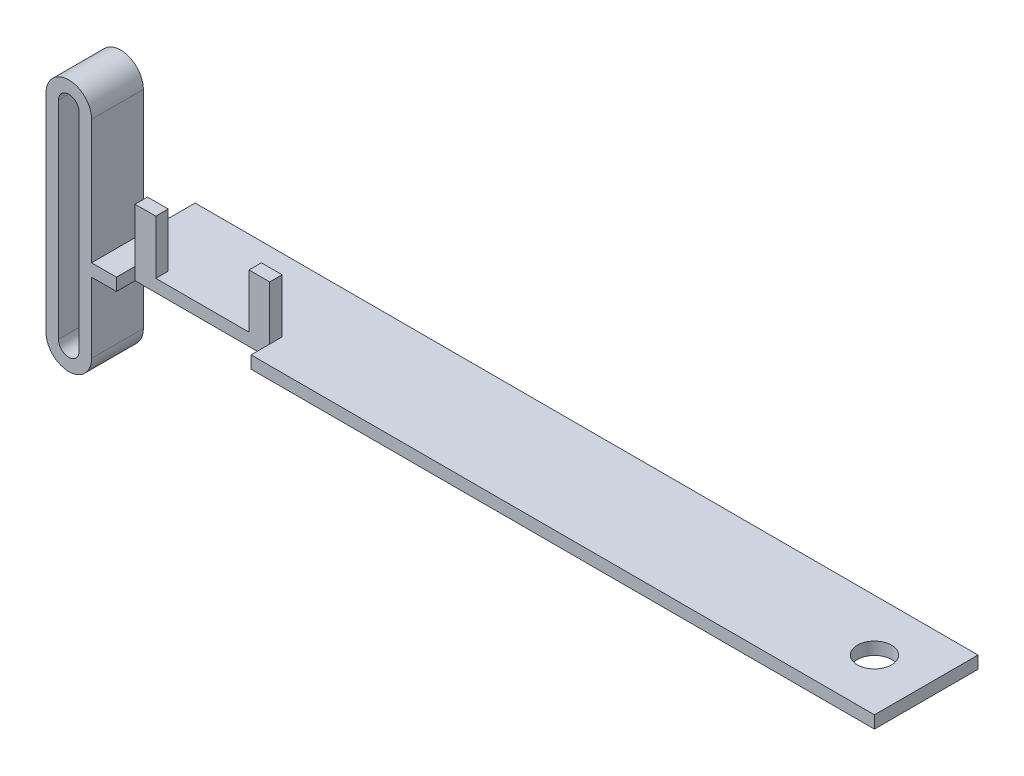
SolidWorks part; units mm, degrees
ref_plane "Front Plane" through (0, 0, 0) normal (0, 0, 1) x (1, 0, 0)
ref_plane "Top Plane" through (0, 0, 0) normal (0, 1, 0) x (1, 0, 0)
ref_plane "Right Plane" through (0, 0, 0) normal (1, 0, 0) x (0, 0, -1)
sketch "Sketch1" plane through (0, 0, 0) normal (0, 1, 0) x (1, 0, 0)
  line L1 (-100, 12.5) -> (100, 12.5)
  line L2 (-100, 12.5) -> (-100, -12.5)
  line L3 (-100, -12.5) -> (100, -12.5)
  line L4 (100, 12.5) -> (100, -12.5)
  line L5 (-100, 12.5) -> (100, -12.5) construction
  line L6 (-100, -12.5) -> (100, 12.5) construction
  circle A4 centre (87.5, 0) radius 4.125
  point P0 (0, 0)
  point P17 (100, 0)
  dimension "D3" = 12.5
  dimension "D4" = 8.25
  dimension "D1" = 25
  dimension "D2" = 200
extrude "Boss-Extrude1" add sketch "Sketch1" along normal blind 3 contours L3 L4 L1 L2 A4 | L3 region at (-0.9456, 0, 0)
sketch "Sketch2" plane through (0, 0, 0) normal (0, 0, 1) x (1, 0, 0)
  line L0 (-94.5, 33) -> (-94.5, -17) construction
  line L1 (-92, 33) -> (-92, -17)
  line L2 (-97, 33) -> (-97, -17)
  line L3 (-89, 33) -> (-89, -17)
  line L4 (-100, 33) -> (-100, -17)
  line L7 (-83, 6.4998) -> (-50.5, 6.4998)
  line L8 (-83, 6.4998) -> (-83, -3.3981)
  line L9 (-83, -3.3981) -> (-50.5, -3.3981)
  line L10 (-50.5, 6.4998) -> (-50.5, -3.3981)
  arc A0 (-92, 33) -> (-97, 33) centre (-94.5, 33) ccw
  arc A1 (-97, -17) -> (-92, -17) centre (-94.5, -17) ccw
  arc A2 (-100, -17) -> (-89, -17) centre (-94.5, -17) ccw
  arc A3 (-89, 33) -> (-100, 33) centre (-94.5, 33) ccw
  point P2 (-94.5, 8)
  dimension "D4" = 5.5
  dimension "D1" = 3
  dimension "D2" = 3
  dimension "D3" = 5
  dimension "D5" = 50
  dimension "D6" = 50
  dimension "D7" = 6
  dimension "D8" = 32.5
extrude "Boss-Extrude2" add sketch "Sketch2" along normal up to surface (12.5 mm away) contours L3 A3 L4 A2 A1 L2 A0 L1 region at (-89.6198, 8, 0) up to face at (0, 1.5, 12.5)
extrude "Cut-Extrude1" cut sketch "Sketch2<2>" against normal through all both and the other way through all contours L2 A1 L1 A0 region at (-94.5, 8, 0)
sketch "Sketch2<2>" plane through (0, 0, 0) normal (0, 0, 1) x (1, 0, 0) same geometry as "Sketch2"
extrude "Cut-Extrude2" cut sketch "Sketch2<3>" against normal up to surface (12.5 mm away) contours L3 A3 L4 A2 A1 L2 A0 L1 region at (-89.6198, 8, 0) up to face at (4, 1.5, -12.5)
sketch "Sketch2<3>" plane through (0, 0, 0) normal (0, 0, 1) x (1, 0, 0) same geometry as "Sketch2"
extrude "Cut-Extrude3" cut sketch "Sketch2<5>" along normal up to surface (12.5 mm away) from offset 8 contours L10 L7 L8 L9 region at (-66.75, 1.5509, 0) up to face at (-94.5, 8, 12.5)
sketch "Sketch2<5>" plane through (0, 0, 0) normal (0, 0, 1) x (1, 0, 0) same geometry as "Sketch2"
sketch "Sketch4" plane through (0, 0, 8) normal (0, 0, 1) x (1, 0, 0)
  line L1 (-83, 3) -> (-78, 3)
  line L2 (-83, 3) -> (-83, 16)
  line L3 (-83, 16) -> (-78, 16)
  line L4 (-78, 3) -> (-78, 16)
  line L5 (-50.5, 3) -> (-55.5, 3)
  line L6 (-50.5, 3) -> (-50.5, 16)
  line L7 (-50.5, 16) -> (-55.5, 16)
  line L8 (-55.5, 3) -> (-55.5, 16)
extrude "Boss-Extrude3" add sketch "Sketch4" against normal blind 3
